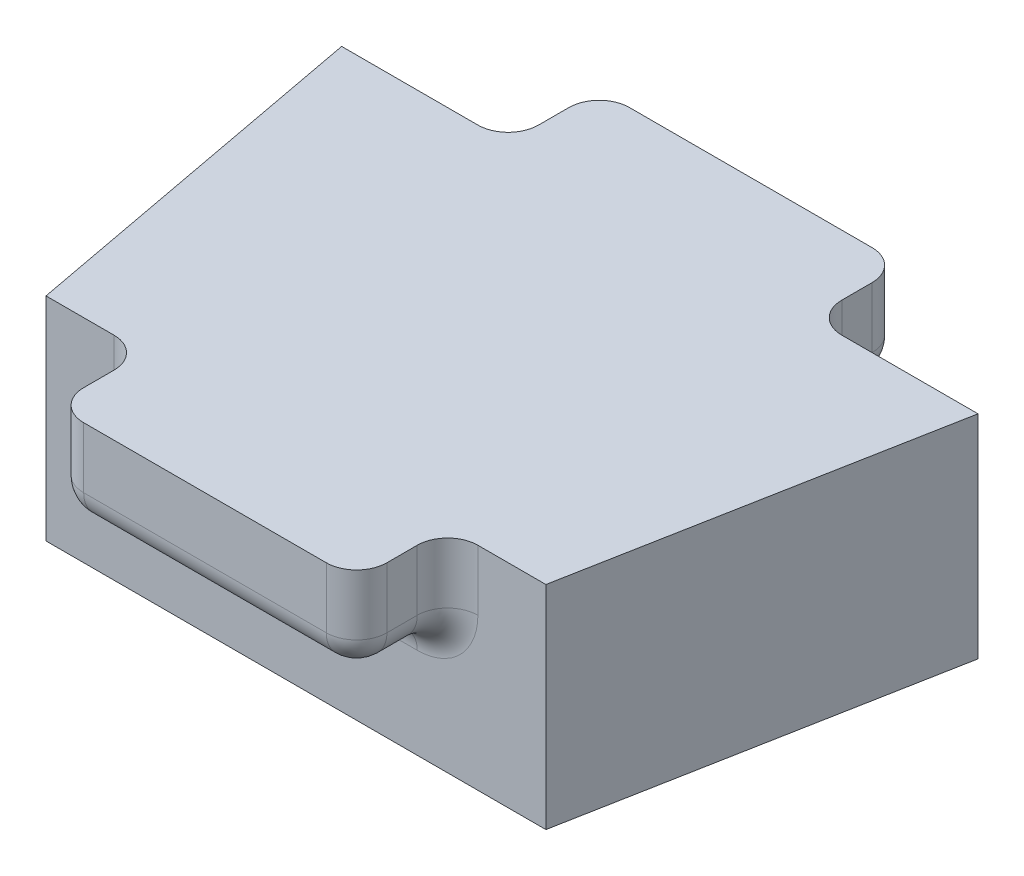
SolidWorks part; units mm, degrees
ref_plane "Front Plane" through (0, 0, 0) normal (0, 0, 1) x (1, 0, 0)
ref_plane "Top Plane" through (0, 0, 0) normal (0, 1, 0) x (1, 0, 0)
ref_plane "Right Plane" through (0, 0, 0) normal (1, 0, 0) x (0, 0, -1)
sketch "Sketch1" plane through (0, 0, 0) normal (0, 1, 0) x (1, 0, 0)
  line L0 (-9.1, 4) -> (9.1, 4)
  line L1 (9.1, 4) -> (7.6, -4)
  line L2 (7.6, -4) -> (-7.6, -4)
  line L3 (-7.6, -4) -> (-9.1, 4)
  line L4 (0, 0) -> (0, 4) construction
  line L5 (-10.4924, 6) -> (10.4924, 6)
  line L6 (10.4924, 6) -> (8.2424, -6)
  line L7 (8.2424, -6) -> (-8.2424, -6)
  line L8 (-8.2424, -6) -> (-10.4924, 6)
  dimension "D1" = 18.2
  dimension "D2" = 15.2
  dimension "D3" = 4
  dimension "D4" = 4
  dimension "D6" = 2
  dimension "D5" = 1
  dimension "D7" = 2
  dimension "D8" = 1
extrude "Boss-Extrude1" add sketch "Sketch1" along normal blind 6
sketch "Sketch2" plane through (0, 6, 0) normal (0, 1, 0) x (1, 0, 0)
  line L4 (-10.4924, 6) -> (-8.2424, -6)
  line L5 (-8.2424, -6) -> (8.2424, -6)
  line L6 (8.2424, -6) -> (10.4924, 6)
  line L7 (10.4924, 6) -> (-10.4924, 6)
  line L8 (-10.4924, 6) -> (-8.2424, -6)
  line L9 (-8.2424, -6) -> (8.2424, -6)
  line L10 (8.2424, -6) -> (10.4924, 6)
  line L11 (10.4924, 6) -> (-10.4924, 6)
  dimension "D1" = 0
extrude "Boss-Extrude2" add sketch "Sketch2" along normal blind 1
sketch "Sketch3" plane through (0, 7, 0) normal (0, 1, 0) x (1, 0, 0)
  line L0 (0, 0) -> (0, -9) construction
  line L1 (10.4924, 6) -> (-10.4924, 6) construction
  line L2 (-5, 6) -> (5, 6)
  line L3 (-5, 6) -> (-5, 9)
  line L4 (-5, 9) -> (5, 9)
  line L5 (5, 6) -> (5, 9)
  line L6 (-8.2424, -6) -> (8.2424, -6) construction
  line L7 (-5, -6) -> (5, -6)
  line L8 (-5, -6) -> (-5, -9)
  line L9 (-5, -9) -> (5, -9)
  line L10 (5, -6) -> (5, -9)
  line L11 (0, 0) -> (0, 9) construction
  point P0 (0, 0)
  dimension "D1" = 10
  dimension "D2" = 3
extrude "Boss-Extrude3" add sketch "Sketch3" against normal blind 3
fillet "Fillet1" radius 1 16 edges at (-5, 5.5, 9) (-5, 4, 7.5) (5, 4, 7.5) (5, 5.5, 9) (5, 5.5, -9) (5, 4, -7.5) (-5, 4, -7.5) (-5, 5.5, -9) (0, 4, -9) (0, 4, 9) (0, 4, 6) (0, 4, -6)
ref_plane "Plane1" [suppressed] through (0, 3, 0) normal (0, -1, 0) x (-1, 0, 0)
split "Split1" [suppressed] bodies to split 103
